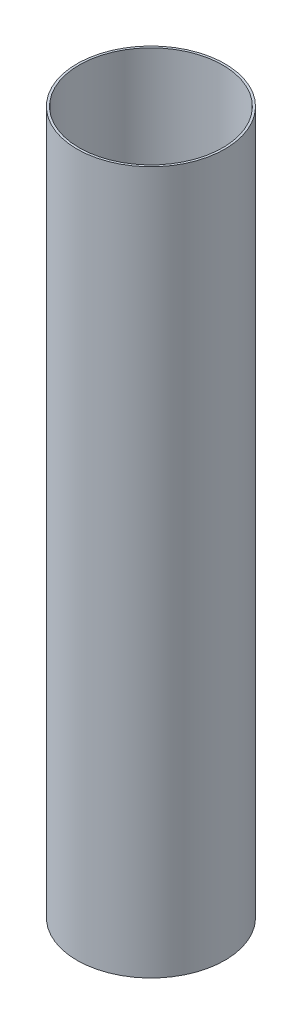
SolidWorks part; units mm, degrees
ref_plane "Front Plane" through (0, 0, 0) normal (1, 0, 0) x (0, 1, 0)
ref_plane "Top Plane" through (0, 0, 0) normal (0, 0, 1) x (0, 1, 0)
ref_plane "Right Plane" through (0, 0, 0) normal (0, 1, 0) x (-1, 0, 0)
ref_plane "Plane1" through (0, 150, 0) normal (0, 1, 0) x (1, 0, 0)
sketch "Sketch1" plane through (0, 150, 0) normal (0, 1, 0) x (1, 0, 0)
  circle A0 centre (0, 0) radius 51.054
  circle A1 centre (0, 0) radius 49.53
  dimension "D1" = 102.108
  dimension "3.9\"" = 99.06
extrude "Boss-Extrude1" add sketch "Sketch1" along normal blind 485 contours A0 | A1
